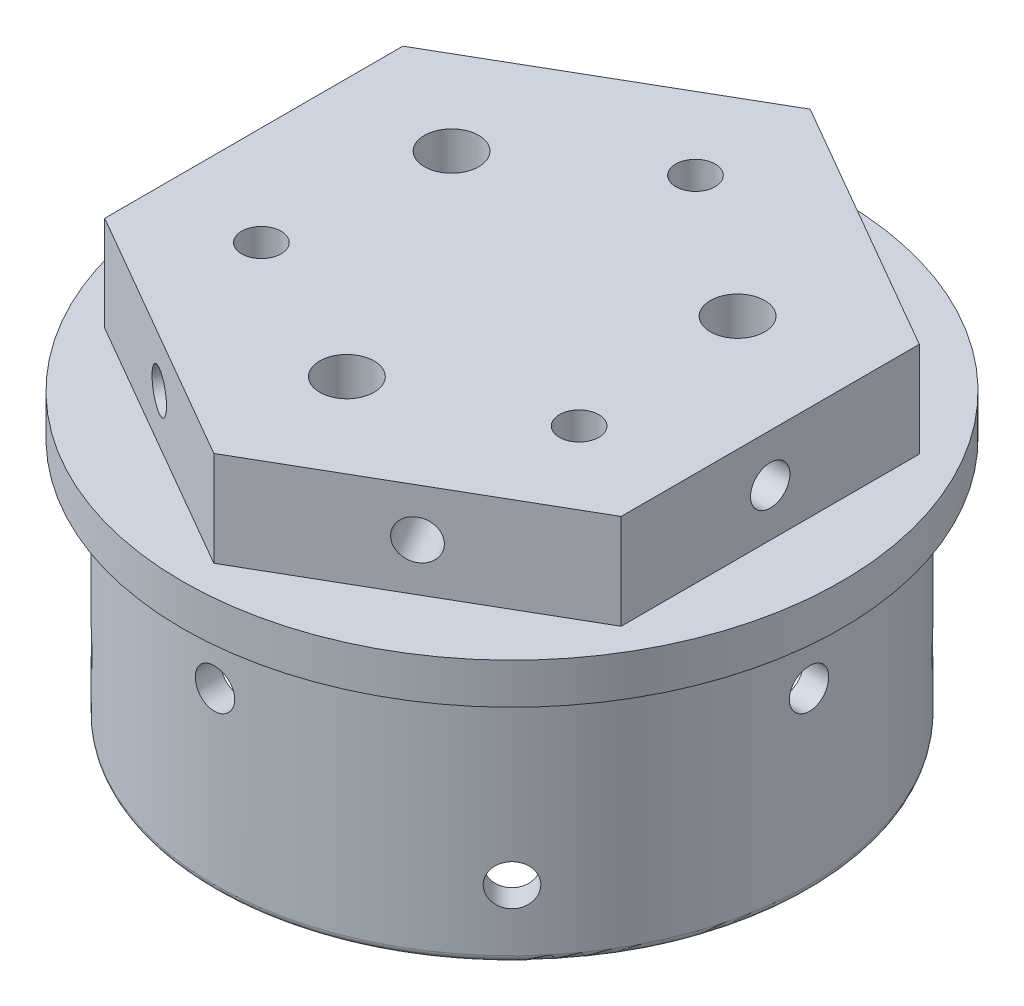
SolidWorks part; units mm, degrees
ref_plane "前视基准面" through (0, 0, 0) normal (0, 0, 1) x (1, 0, 0)
ref_plane "上视基准面" through (0, 0, 0) normal (0, 1, 0) x (1, 0, 0)
ref_plane "右视基准面" through (0, 0, 0) normal (1, 0, 0) x (0, 0, -1)
sketch "草图1" plane through (0, 0, 0) normal (0, 1, 0) x (1, 0, 0)
  line L0 (0, 0) -> (0, 33.3478) construction
  line L1 (0, 0) -> (11.2563, 0) construction
  line L2 (-11.6913, -6.75) -> (0, 0) construction
  line L3 (0, 0) -> (11.6913, -6.75) construction
  line L4 (0, 0) -> (-10.5222, 6.075) construction
  line L5 (10.5222, 6.075) -> (0, 0) construction
  circle A0 centre (0, 0) radius 19
  circle A1 centre (0, 13.5) radius 1.45
  circle A2 centre (0, 0) radius 13.5 construction
  circle A3 centre (-11.6913, -6.75) radius 1.45
  circle A4 centre (11.6913, -6.75) radius 1.45
  circle A5 centre (0, 0) radius 12.15 construction
  circle A6 centre (-10.5222, 6.075) radius 2
  circle A7 centre (0, -12.15) radius 2
  circle A8 centre (10.5222, 6.075) radius 2
  dimension "D1" = 38
  dimension "D2" = 27
  dimension "D3" = 2.9
  dimension "D6" = 24.3
  dimension "D8" = 4
  dimension "D4" = 120
  dimension "D5" = 120
  dimension "D7" = 60
  dimension "D9" = 60
extrude "凸台-拉伸1" add sketch "草图1" along normal blind 12
sketch "草图2" plane through (0, 12, 0) normal (0, 1, 0) x (1, 0, 0)
  line L0 (0, 21.9393) -> (0, 0) construction
  line L1 (0, 21.9393) -> (-19, 10.9697)
  line L2 (-19, 10.9697) -> (-19, -10.9697)
  line L3 (-19, -10.9697) -> (0, -21.9393)
  line L4 (0, -21.9393) -> (19, -10.9697)
  line L5 (19, -10.9697) -> (19, 10.9697)
  line L6 (19, 10.9697) -> (0, 21.9393)
  circle A0 centre (0, 0) radius 19 construction
  circle A1 centre (0, 13.5) radius 1.45
  circle A2 centre (0, 13.5) radius 1.45 construction
  circle A3 centre (-10.5222, 6.075) radius 2
  circle A4 centre (-10.5222, 6.075) radius 2 construction
  circle A5 centre (10.5222, 6.075) radius 2
  circle A6 centre (10.5222, 6.075) radius 2 construction
  circle A7 centre (-11.6913, -6.75) radius 1.45
  circle A8 centre (-11.6913, -6.75) radius 1.45 construction
  circle A9 centre (0, -12.15) radius 2
  circle A10 centre (0, -12.15) radius 2 construction
  circle A11 centre (11.6913, -6.75) radius 1.45
  circle A12 centre (11.6913, -6.75) radius 1.45 construction
  dimension "D1" = 38
extrude "凸台-拉伸2" add sketch "草图2" against normal blind 7
sketch "草图3" plane through (9.5, 0, 16.4545) normal (0.5, 0, 0.866) x (0.866, 0, -0.5)
  line L1 (0, 12) -> (0, 5) construction
  line L2 (-10.9697, 12) -> (10.9697, 12) construction
  circle A1 centre (0, 8.5) radius 1.45
  dimension "D1" = 2.9
extrude "切除-拉伸1" cut sketch "草图3" against normal blind 8
sketch "草图4" plane through (-9.5, 0, 16.4545) normal (-0.5, 0, 0.866) x (0.866, 0, 0.5)
  line L0 (0, 5) -> (0, 12) construction
  line L1 (-10.9697, 12) -> (10.9697, 12) construction
  circle A0 centre (0, 8.5) radius 1.45
  dimension "D1" = 2.9
extrude "切除-拉伸2" cut sketch "草图4" against normal blind 8
sketch "草图5" plane through (-19, 0, 0) normal (-1, 0, 0) x (0, 0, 1)
  line L0 (0, 5) -> (0, 12) construction
  line L1 (-10.9697, 12) -> (10.9697, 12) construction
  circle A0 centre (0, 8.5) radius 1.45
  dimension "D1" = 2.9
extrude "切除-拉伸3" cut sketch "草图5" against normal blind 8
sketch "草图6" plane through (19, 0, 0) normal (1, 0, 0) x (0, 0, -1)
  line L0 (0, 12) -> (0, 5) construction
  line L1 (-10.9697, 12) -> (10.9697, 12) construction
  circle A0 centre (0, 8.5) radius 1.45
  dimension "D1" = 2.9
extrude "切除-拉伸4" cut sketch "草图6" against normal blind 8
sketch "草图7" plane through (9.5, 0, -16.4545) normal (0.5, 0, -0.866) x (-0.866, 0, -0.5)
  line L0 (0, 12) -> (0, 5) construction
  line L1 (-10.9697, 12) -> (10.9697, 12) construction
  circle A0 centre (0, 8.5) radius 1.45
  dimension "D1" = 2.9
extrude "切除-拉伸5" cut sketch "草图7" against normal blind 8
sketch "草图8" plane through (0, 0, 0) normal (0, -1, 0) x (1, 0, 0)
  circle A0 centre (0, 0) radius 24
  dimension "D1" = 48
extrude "切除-拉伸6" cut sketch "草图8" against normal up to surface (5 mm away) up to face at (16.5682, 5, 9.5656)
sketch "草图10" plane through (0, 5, 0) normal (0, -1, 0) x (1, 0, 0)
  circle A0 centre (0, 0) radius 24.25
  dimension "D1" = 48.5
extrude "凸台-拉伸3" add sketch "草图10" along normal blind 3
sketch "草图11" plane through (0, 2, 0) normal (0, -1, 0) x (1, 0, 0)
  circle A0 centre (0, 0) radius 21.9
  dimension "D1" = 43.8
extrude "凸台-拉伸4" add sketch "草图11" along normal blind 18
sketch "草图12" plane through (0, -16, 0) normal (0, -1, 0) x (1, 0, 0)
  line L8 (-17.6569, -10.6274) -> (-10.6274, -17.6569)
  line L9 (-4.9706, -20) -> (4.9706, -20)
  line L10 (10.6274, -17.6569) -> (17.6569, -10.6274)
  line L11 (20, -4.9706) -> (20, 4.9706)
  line L12 (17.6569, 10.6274) -> (10.6274, 17.6569)
  line L13 (4.9706, 20) -> (-4.9706, 20)
  line L14 (-10.6274, 17.6569) -> (-17.6569, 10.6274)
  line L15 (-20, 4.9706) -> (-20, -4.9706)
  circle A0 centre (0, 0) radius 20 construction
  arc A1 (-4.9706, 20) -> (-10.6274, 17.6569) centre (-4.9706, 12) ccw
  arc A2 (10.6274, 17.6569) -> (4.9706, 20) centre (4.9706, 12) ccw
  arc A3 (20, 4.9706) -> (17.6569, 10.6274) centre (12, 4.9706) ccw
  arc A4 (17.6569, -10.6274) -> (20, -4.9706) centre (12, -4.9706) ccw
  arc A5 (4.9706, -20) -> (10.6274, -17.6569) centre (4.9706, -12) ccw
  arc A6 (-10.6274, -17.6569) -> (-4.9706, -20) centre (-4.9706, -12) ccw
  arc A7 (-17.6569, -10.6274) -> (-20, -4.9706) centre (-12, -4.9706) cw
  arc A8 (-17.6569, 10.6274) -> (-20, 4.9706) centre (-12, 4.9706) ccw
  point P1 (-20.1161, -8.3324)
  dimension "D1" = 40
  dimension "D2" = 8
extrude "切除-拉伸7" cut sketch "草图12" against normal blind 18
sketch "草图13" plane through (20, 0, 0) normal (-1, 0, 0) x (0, 0, 1)
  line L0 (-21.9, 2) -> (21.9, 2) construction
  circle A0 centre (0, -3) radius 1.45
  point P2 (0, -6.287)
  point P3 (0, -7.3627)
  dimension "D2" = 2.9
  dimension "D1" = 5
sketch "草图14" plane through (14.1421, 0, -14.1421) normal (-0.7071, 0, 0.7071) x (0.7071, 0, 0.7071)
  line L0 (-21.9, -16) -> (21.9, -16) construction
  circle A0 centre (0, -11) radius 1.45
  dimension "D2" = 2.9
  dimension "D1" = 5
sketch "草图15" plane through (0, 0, -20) normal (0, 0, 1) x (1, 0, 0)
  line L0 (-21.9, 2) -> (21.9, 2) construction
  circle A0 centre (0, -3) radius 1.45
  dimension "D2" = 2.9
  dimension "D1" = 5
sketch "草图16" plane through (-14.1421, 0, -14.1421) normal (0.7071, 0, 0.7071) x (0.7071, 0, -0.7071)
  line L0 (-21.9, -16) -> (21.9, -16) construction
  circle A0 centre (0, -11) radius 1.5
  dimension "D1" = 3
  dimension "D2" = 5
extrude "切除-拉伸8" cut sketch "草图13" along normal through all and the other way through all
extrude "切除-拉伸9" cut sketch "草图14" against normal through all and the other way through all contours A0
extrude "切除-拉伸10" cut sketch "草图15" against normal through all and the other way through all contours A0
extrude "切除-拉伸11" cut sketch "草图16" against normal through all and the other way through all contours A0
fillet "圆角1" radius 0.5 17 edges at (0, -16, -21.9) (-14.1421, -16, 14.1421) (-19.391, -16, 8.032) (-20, -16, 0) (-19.391, -16, -8.032) (-14.1421, -16, -14.1421) (-8.032, -16, -19.391) (0, -16, -20) (8.032, -16, -19.391) (14.1421, -16, -14.1421) (19.391, -16, -8.032) (20, -16, 0) (19.391, -16, 8.032) (14.1421, -16, 14.1421) (8.032, -16, 19.391) (0, -16, 20) (-8.032, -16, 19.391)
fillet "圆角2" radius 2 16 edges at (0, 2, 20) (8.032, 2, 19.391) (14.1421, 2, 14.1421) (19.391, 2, 8.032) (20, 2, 0) (19.391, 2, -8.032) (14.1421, 2, -14.1421) (8.032, 2, -19.391) (0, 2, -20) (-8.032, 2, -19.391) (-14.1421, 2, -14.1421) (-19.391, 2, -8.032) (-20, 2, 0) (-19.391, 2, 8.032) (-14.1421, 2, 14.1421) (-8.032, 2, 19.391)
